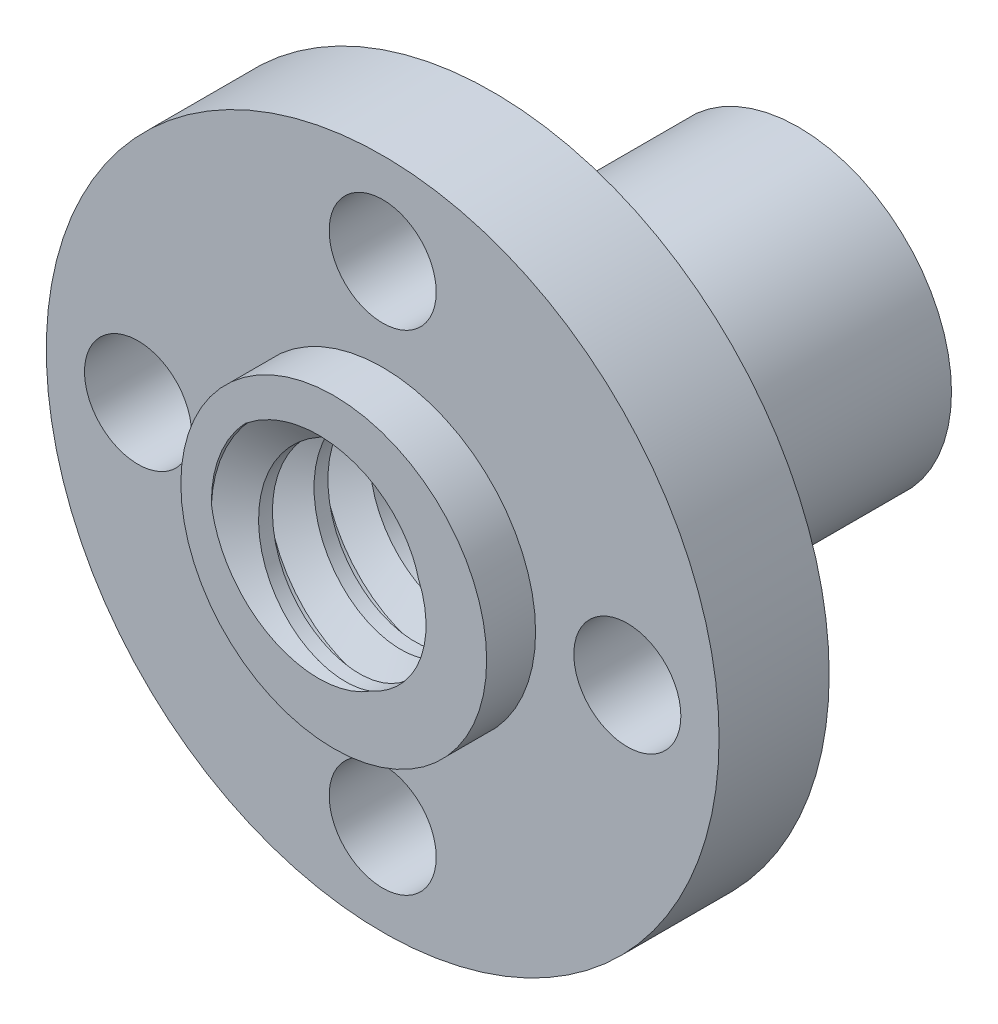
SolidWorks part; units mm, degrees
ref_plane "Front" through (0, 0, 0) normal (0, 0, 1) x (1, 0, 0)
ref_plane "Top" through (0, 0, 0) normal (0, 1, 0) x (1, 0, 0)
ref_plane "Right" through (0, 0, 0) normal (1, 0, 0) x (0, 0, -1)
sketch "Sketch1" plane through (0, 0, 0) normal (0, 0, 1) x (1, 0, 0)
  circle A0 centre (0, 0) radius 11
  dimension "D1" = 22
extrude "Boss-Extrude1" add sketch "Sketch1" along normal blind 3.6
sketch "Sketch2" plane through (0, 0, 3.6) normal (0, 0, 1) x (1, 0, 0)
  circle A0 centre (0, 0) radius 5
  dimension "D1" = 10
extrude "Boss-Extrude2" add sketch "Sketch2" along normal blind 1.6 contours A0
sketch "Sketch3" plane through (0, 0, 0) normal (0, 0, -1) x (-1, 0, 0)
  circle A0 centre (0, 0) radius 5
  dimension "D1" = 10
extrude "Boss-Extrude3" add sketch "Sketch3" along normal blind 10
sketch "Sketch4" plane through (0, 0, -10) normal (0, 0, -1) x (-1, 0, 0)
  circle A0 centre (0, 0) radius 4
  circle A1 centre (0, 0) radius 5 construction
  dimension "D1" = 1
extrude "Cut-Extrude1" cut sketch "Sketch4" against normal up to next contours A0
thread "Thread1" pitch 1.8143 method extrude profile "Thread Profile1" start angle 0, offset 0, length 15.2, pitch 1.8143, diameter 8
ref_plane "Plane1" through (4, 0, -10) normal (0, -1, 0) x (1, 0, 0)
sketch "Thread Profile1" plane through (4, 0, -10) normal (0, -1, 0) x (1, 0, 0)
  line L0 (0, 0) -> (0, 1.8143) construction
  line L11 (0, 0) -> (0, 1.5875)
  line L12 (0, 1.5875) -> (-0.982, 1.0205)
  line L13 (-0.982, 1.0205) -> (-0.982, 0.567)
  line L15 (-0.982, 0.567) -> (0, 0)
  line L17 (-0.982, 0.7937) -> (0, 0.7937) construction
  point P2 (0, 0)
  dimension "Pitch" = 1.8143
  dimension "Profile_Angle" = 60
  dimension "Profile_Land" = 0.4536
  dimension "Profile_Height" = 0.982
sketch "Sketch7" plane through (0, 0, 5.2) normal (0, 0, 1) x (1, 0, 0)
  circle A0 centre (0, 0) radius 5
extrude "Cut-Extrude2" cut sketch "Sketch7" along normal blind 2
sketch "Sketch8" plane through (0, 0, 3.6) normal (0, 0, 1) x (1, 0, 0)
  line L0 (-11, 0) -> (11, 0) construction
  line L1 (0, 11) -> (0, -11) construction
  circle A0 centre (0, 0) radius 11 construction
  circle A1 centre (-8, 0) radius 1.75
  circle A2 centre (8, 0) radius 1.75
  circle A3 centre (0, 8) radius 1.75
  circle A4 centre (0, -8) radius 1.75
  circle A5 centre (8, 0) radius 1.75
  circle A6 centre (-8, 0) radius 1.75
  circle A7 centre (0, -8) radius 1.75
  circle A8 centre (0, 8) radius 1.75
  point P26 (0, 0)
  dimension "D1" = 4
  dimension "D2" = 16
  dimension "D3" = 8
extrude "Cut-Extrude3" cut sketch "Sketch8" against normal up to next contours A1 | A3 | A2 | A4 region at (-8, 0, 3.6) region at (8, 0, 3.6) region at (0, 8, 3.6) region at (0, -8, 3.6)
